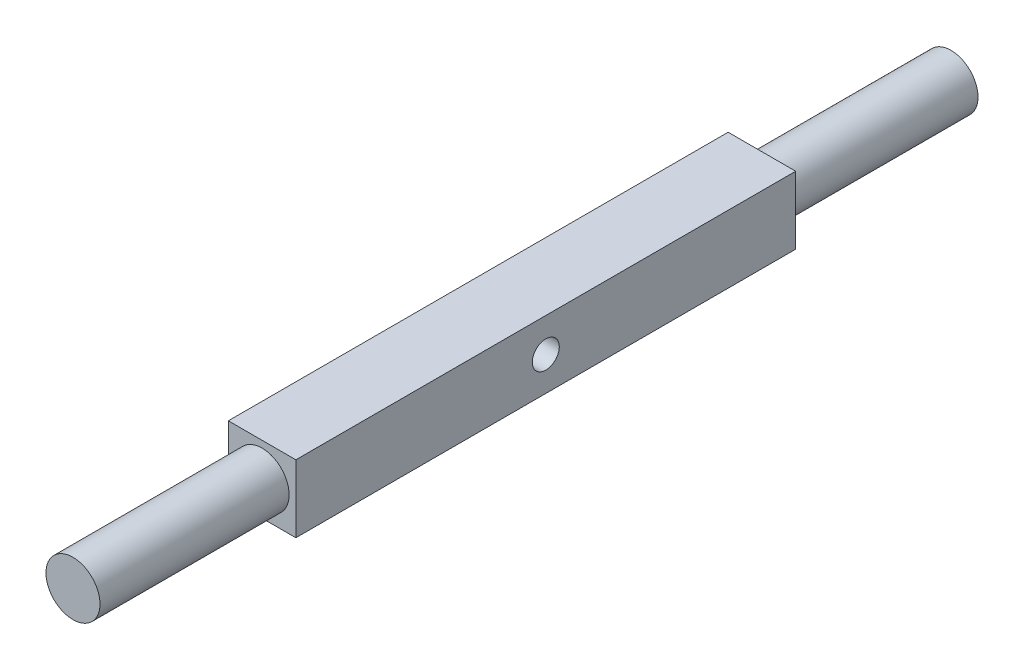
SolidWorks part; units mm, degrees
material "6061-T6 (SS)"
ref_plane "Front Plane" through (0, 0, 0) normal (0, 0, 1) x (1, 0, 0)
ref_plane "Top Plane" through (0, 0, 0) normal (0, 1, 0) x (1, 0, 0)
ref_plane "Right Plane" through (0, 0, 0) normal (1, 0, 0) x (0, 0, -1)
sketch "Sketch1" plane through (0, 0, 0) normal (0, 0, 1) x (1, 0, 0)
  line L0 (0, 0) -> (25, 0)
  line L1 (25, 0) -> (25, 25)
  line L2 (25, 25) -> (0, 25)
  line L3 (0, 25) -> (0, 0)
extrude "Boss-Extrude1" add sketch "Sketch1" along normal blind 92.5 and the other way blind 92.5
sketch "Sketch2" plane through (25, 0, 0) normal (1, 0, 0) x (0, 0, -1)
  line L0 (92.5, 12.5) -> (0, 12.5)
  line L1 (92.5, 0) -> (92.5, 25) construction
  circle A0 centre (0, 12.5) radius 5
extrude "Cut-Extrude1" cut sketch "Sketch2" against normal through all contours A0 region at (25, 12.5, 4.8586)
sketch "Sketch3" plane through (0, 0, 92.5) normal (0, 0, 1) x (1, 0, 0)
  line L0 (25, 12.5) -> (12.5, 12.5)
  line L1 (25, 0) -> (25, 25) construction
  circle A0 centre (12.5, 12.5) radius 10
extrude "Boss-Extrude2" add sketch "Sketch3" along normal blind 70 contours A0 region at (2.7828, 12.5, 92.5)
sketch "Sketch4" plane through (0, 0, -92.5) normal (0, 0, -1) x (-1, 0, 0)
  line L0 (-25, 12.5) -> (-12.5, 12.5)
  line L1 (-25, 0) -> (-25, 25) construction
  circle A0 centre (-12.5, 12.5) radius 10
extrude "Boss-Extrude3" add sketch "Sketch4" along normal blind 70 contours A0 region at (12.5, 2.7828, -92.5)
sketch "Sketch5" [suppressed] plane through (0, 0, 0) normal (0, -1, 0) x (1, 0, 0)
  line L0 (12.5, -162.5) -> (12.5, -141.25)
  line L1 (2.5, -162.5) -> (22.5, -162.5) construction
  line L2 (12.5, 162.5) -> (12.5, 141.25)
  line L3 (22.5, 162.5) -> (2.5, 162.5) construction
  line L4 (25, 5) -> (12.5, 5)
  line L6 (12.5, -141.25) -> (-65.6706, -141.25)
  line L7 (12.5, 141.25) -> (-65.6706, 141.25)
  line L8 (12.5, 5) -> (159.5125, 5)
